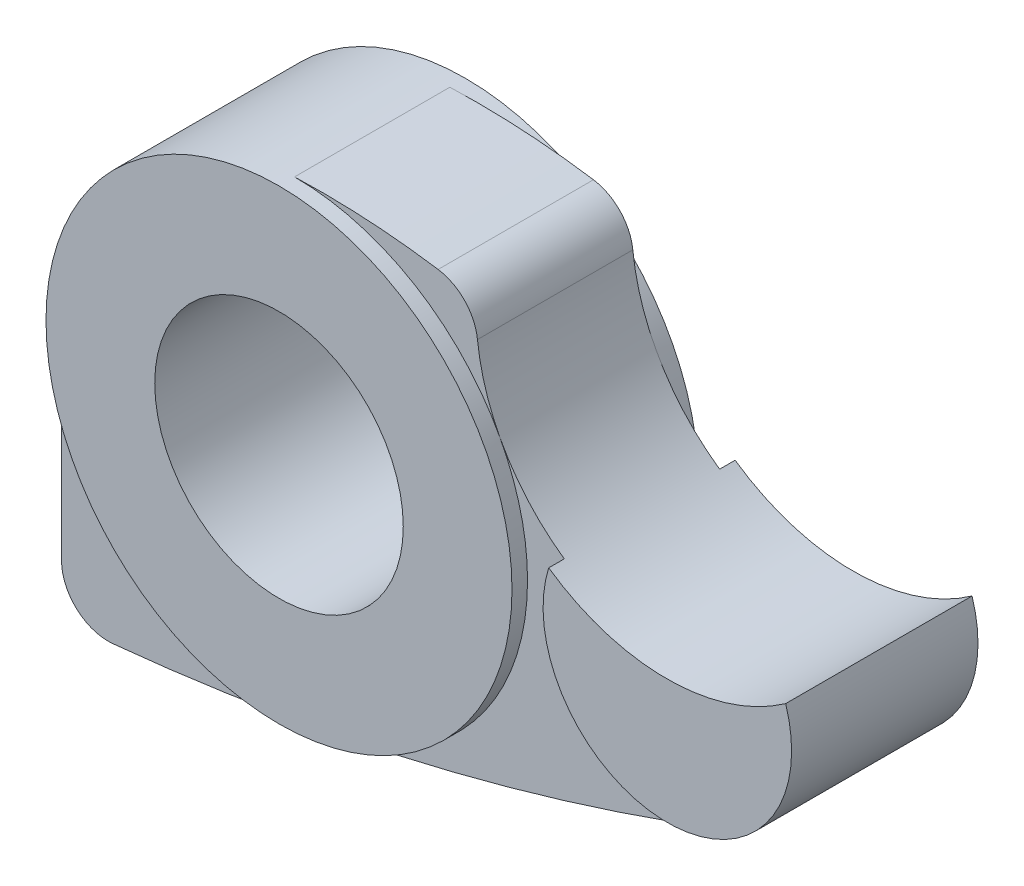
SolidWorks part; units mm, degrees
ref_plane "前视基准面" through (0, 0, 0) normal (0, 0, 1) x (1, 0, 0)
ref_plane "上视基准面" through (0, 0, 0) normal (0, 1, 0) x (1, 0, 0)
ref_plane "右视基准面" through (0, 0, 0) normal (1, 0, 0) x (0, 0, -1)
other "Configuration Table"
sketch "草图1" plane through (0, 0, 0) normal (0, 0, 1) x (1, 0, 0)
  circle A0 centre (0, 0) radius 15
  circle A1 centre (0, 0) radius 8
  dimension "D1" = 16
  dimension "D2" = 30
extrude "凸台-拉伸1" add sketch "草图1" along normal mid plane 12
sketch "草图2" plane through (0, 0, 0) normal (0, 0, 1) x (1, 0, 0)
  line L0 (-15, 0) -> (-15, -13.8874)
  arc A0 (-11.7086, -16.8732) -> (27.889, -7.4601) centre (-26.28, 132.4174) ccw
  circle A1 centre (0, 0) radius 15 construction
  arc A2 (17.3642, 2.3863) -> (32.6176, 2.4439) centre (25, 0) ccw
  arc A3 (11.7773, 11.821) -> (32.6176, 2.4439) centre (24.95, 13.2499) ccw
  circle A5 centre (0, 0) radius 15
  arc A6 (9.2452, 14.4634) -> (0, 15) centre (1.7381, -34.9698) ccw
  arc A7 (11.7773, 11.821) -> (9.2452, 14.4634) centre (8.7948, 11.4975) ccw
  arc A8 (-15, -13.8874) -> (-11.7086, -16.8732) centre (-12, -13.8874) ccw
  point P5 (0, 0)
  point P14 (4.4228, -28.1673)
  point P16 (11.7231, 14.0315)
  point P18 (11.7231, 14.0315)
  point P19 (11.7231, 14.0315)
  point P20 (0, 0)
  point P21 (0, 0)
  dimension "D1" = 300
  dimension "D2" = 16
  dimension "D3" = 25
  dimension "D4" = 26.5
  dimension "D5" = 50
  dimension "D6" = 3
extrude "凸台-拉伸3" add sketch "草图2" along normal mid plane 12 separate body contours A3 A2 region at (25.011, -2.9229, 0)
extrude "凸台-拉伸4" add sketch "草图2<4>" along normal mid plane 10 contours A5 A0 A2 A3 | L0 A8 A0 A5 | A3 A7 A6 A5 region at (-10.7867, -12.7462, 0) region at (8.849, 12.8899, 0) region at (16.0301, -6.9317, 0)
sketch "草图2<4>" plane through (0, 0, 0) normal (0, 0, 1) x (1, 0, 0) same geometry as "草图2"
